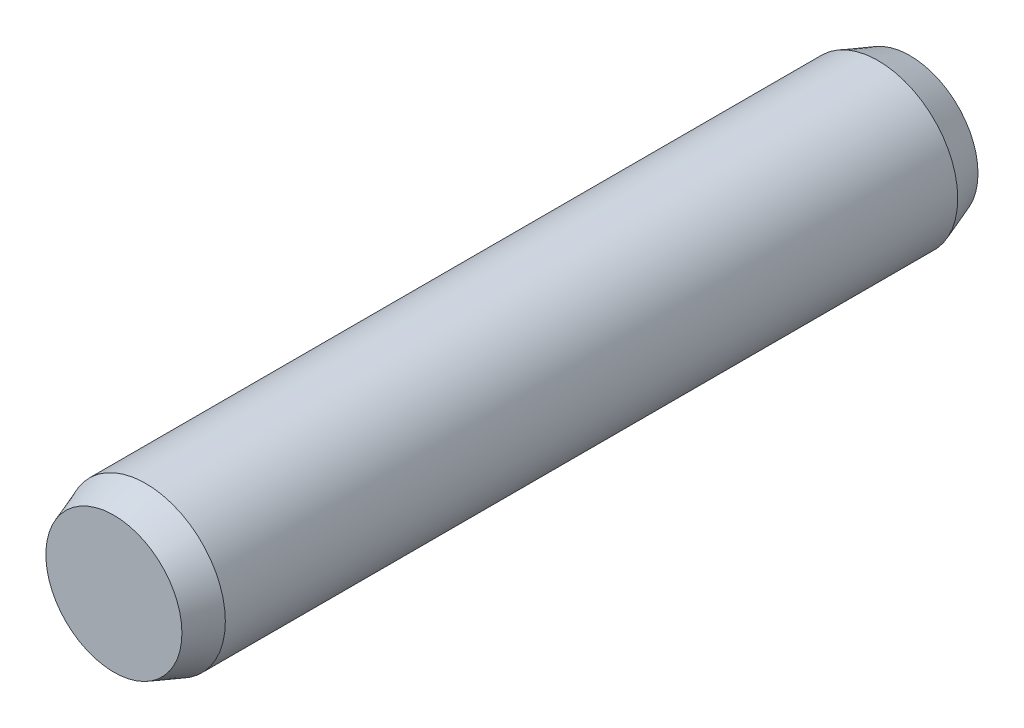
SolidWorks part; units mm, degrees
material "Acier allié"
ref_plane "Plan de face" through (0, 0, 0) normal (0, 0, 1) x (1, 0, 0)
ref_plane "Plan de dessus" through (0, 0, 0) normal (0, 1, 0) x (1, 0, 0)
ref_plane "Plan de droite" through (0, 0, 0) normal (1, 0, 0) x (0, 0, -1)
sketch "E_CORPS" plane through (0, 0, 0) normal (0, 0, 1) x (1, 0, 0)
  circle A0 centre (0, 0) radius 0.4
  dimension "DIAM" = 0.8
extrude "CORPS" add sketch "E_CORPS" against normal mid plane 4
chamfer "CHANF" distance 0.16 angle 20 2 edges at (0.4, 0, 2) (0.4, 0, -2) tangent propagation no first distance on face at (0.4, 0, -2)
other "PropertyManager"
